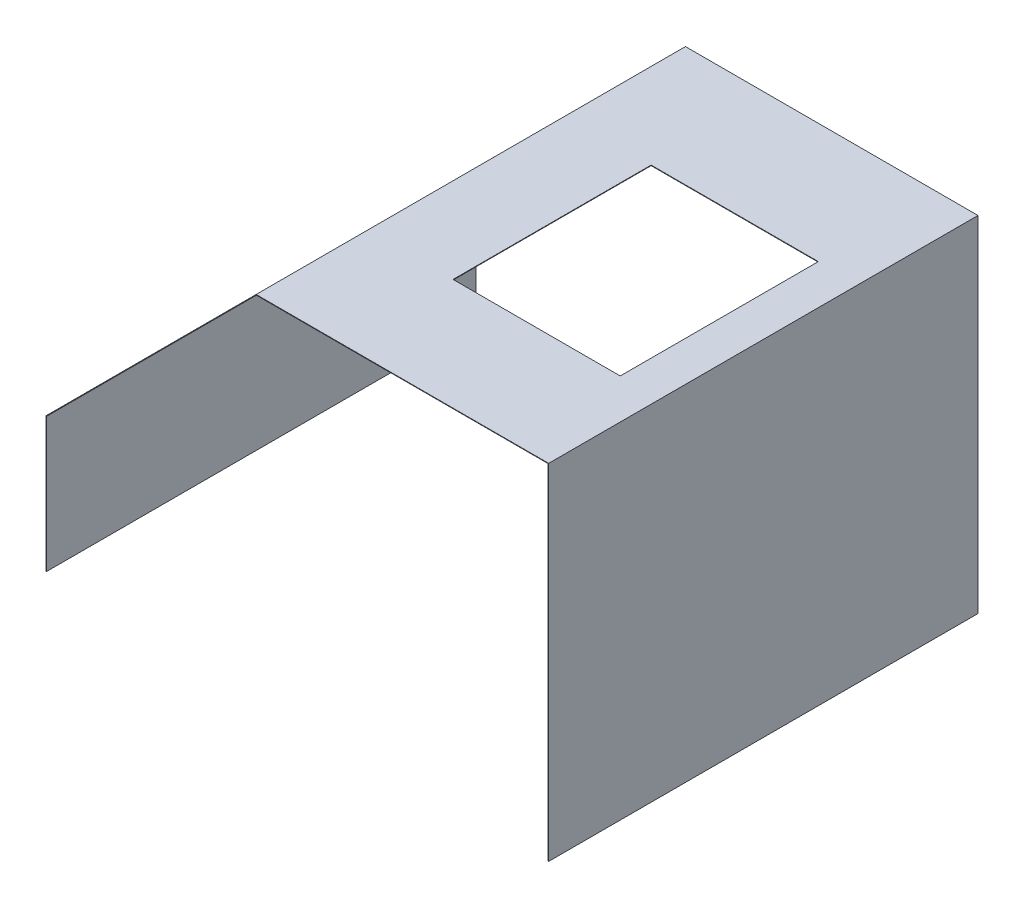
SolidWorks part; units mm, degrees
other "Carpeta de soldadura"
ref_plane "Alzado" through (0, 0, 0) normal (0, 0, 1) x (1, 0, 0)
ref_plane "Planta" through (0, 0, 0) normal (0, 1, 0) x (1, 0, 0)
ref_plane "Vista lateral" through (0, 0, 0) normal (1, 0, 0) x (0, 0, -1)
sketch "Croquis1" plane through (0, 0, 0) normal (0, 0, 1) x (1, 0, 0)
  line L0 (0, 0) -> (765, 0)
  line L1 (765, 0) -> (765, 525)
  line L2 (765, 525) -> (320, 525)
  line L3 (320, 525) -> (0, 205)
  line L4 (0, 205) -> (0, 0)
  dimension "D1" = 765
  dimension "D2" = 525
  dimension "D3" = 445
  dimension "D4" = 205
extrude "Saliente-Extruir1" add sketch "Croquis1" along normal blind 0.8357
sketch "Croquis2" plane through (0, 0, 0.8357) normal (0, 0, 1) x (1, 0, 0)
  line L15 (765.8357, 525.8357) -> (319.6539, 525.8357)
  line L16 (319.6539, 525.8357) -> (-0.8357, 205.3461)
  line L22 (-0.8357, 205.3461) -> (-0.8357, 0)
  line L24 (765.8357, 0) -> (765.8357, 525.8357)
  line L25 (0, 205) -> (0, 0)
  line L26 (0, 0) -> (765, 0)
  line L27 (765, 0) -> (765, 525)
  line L28 (765, 525) -> (320, 525)
  line L29 (320, 525) -> (0, 205)
  line L30 (0, 205) -> (0, 0)
  line L32 (765, 0) -> (765, 525)
  line L33 (765, 525) -> (320, 525)
  line L34 (320, 525) -> (0, 205)
  line L35 (0, 0) -> (-0.8357, 0)
  line L36 (-0.8357, 205.3461) -> (-0.8357, -0.8357) construction
  line L37 (-0.8357, -0.8357) -> (765.8357, -0.8357) construction
  line L38 (0, 0) -> (765, 0) construction
  line L39 (765, 0) -> (765.8357, 0)
  line L40 (765.8357, -0.8357) -> (765.8357, 525.8357) construction
  dimension "D1" = 0
  dimension "D2" = 0.8357
extrude "Saliente-Extruir2" add sketch "Croquis2" along normal blind 12.7
ref_plane "Plano1" through (0, 0, 13.5357) normal (0, 0, 1) x (1, 0, 0)
sketch "Croquis3" plane through (0, 0, 13.5357) normal (0, 0, 1) x (1, 0, 0)
  line L0 (450, 525.8357) -> (450, 525)
  line L1 (765.8357, 0) -> (765.8357, 525.8357) construction
  line L2 (765.8357, 0) -> (765.8357, 525.8357)
  line L3 (450, 525) -> (320, 525)
  line L5 (320, 525) -> (0, 205)
  line L6 (765.8357, 525.8357) -> (319.6539, 525.8357) construction
  line L7 (765, 525) -> (765, 0)
  line L8 (765, 0) -> (765.8357, 0)
  line L9 (765, 525) -> (705, 525)
  line L10 (320, 525) -> (765, 525) construction
  line L11 (705, 525) -> (705, 525.8357)
  line L12 (705, 525.8357) -> (765.8357, 525.8357)
  line L13 (0, 205) -> (0, 0)
  line L14 (0, 0) -> (-0.8357, 0)
  line L15 (-0.8357, 0) -> (-0.8357, 205.3461)
  line L16 (-0.8357, 205.3461) -> (319.6539, 525.8357)
  line L17 (319.6539, 525.8357) -> (450, 525.8357)
  dimension "D1" = 130
  dimension "D2" = 255
extrude "Saliente-Extruir3" add sketch "Croquis3" along normal blind 642.126
sketch "Croquis4" plane through (0, 0, 13.5357) normal (0, 0, 1) x (1, 0, 0)
  line L4 (705, 525.8357) -> (450, 525.8357)
  line L5 (450, 525.8357) -> (450, 525)
  line L6 (450, 525) -> (705, 525)
  line L7 (705, 525) -> (705, 525.8357)
  line L8 (705, 525.8357) -> (450, 525.8357)
  line L9 (450, 525.8357) -> (450, 525)
  line L10 (450, 525) -> (705, 525)
  line L11 (705, 525) -> (705, 525.8357)
  dimension "D1" = 0
extrude "Saliente-Extruir4" add sketch "Croquis4" along normal blind 170
sketch "Croquis5" plane through (0, 0, 655.6617) normal (0, 0, 1) x (1, 0, 0)
  line L4 (705, 525) -> (705, 525.8357)
  line L5 (705, 525.8357) -> (450, 525.8357)
  line L6 (450, 525.8357) -> (450, 525)
  line L7 (450, 525) -> (705, 525)
  line L8 (705, 525) -> (705, 525.8357)
  line L9 (705, 525.8357) -> (450, 525.8357)
  line L10 (450, 525.8357) -> (450, 525)
  line L11 (450, 525) -> (705, 525)
  dimension "D1" = 0
extrude "Saliente-Extruir5" add sketch "Croquis5" against normal blind 170
sketch "Croquis6" plane through (-103.0909, 103.0909, 0) normal (-0.7071, 0.7071, 0) x (0, 0, 1)
  line L0 (0.8357, 597.8514) -> (655.6617, 144.6107) construction
  line L1 (0.8357, 144.6107) -> (655.6617, 597.8514) construction
  line L3 (48.2487, 546.2311) -> (608.2487, 546.2311)
  line L4 (48.2487, 546.2311) -> (48.2487, 196.2311)
  line L5 (48.2487, 196.2311) -> (608.2487, 196.2311)
  line L6 (608.2487, 546.2311) -> (608.2487, 196.2311)
  line L7 (48.2487, 546.2311) -> (608.2487, 196.2311) construction
  line L8 (48.2487, 196.2311) -> (608.2487, 546.2311) construction
  point P8 (328.2487, 371.2311)
  dimension "D1" = 350
  dimension "D2" = 560
extrude "Cortar-Extruir1" cut sketch "Croquis6" against normal blind 190
sketch "Croquis7" plane through (0, 0, 0.8357) normal (0, 0, 1) x (1, 0, 0)
  line L0 (0, 0) -> (765, 0)
  line L1 (765, 0) -> (765, 525)
  line L2 (765, 525) -> (320, 525)
  line L3 (320, 525) -> (0, 205)
  line L4 (0, 205) -> (0, 0)
extrude "Cortar-Extruir2" cut sketch "Croquis7" against normal blind 174 and the other way blind 198
